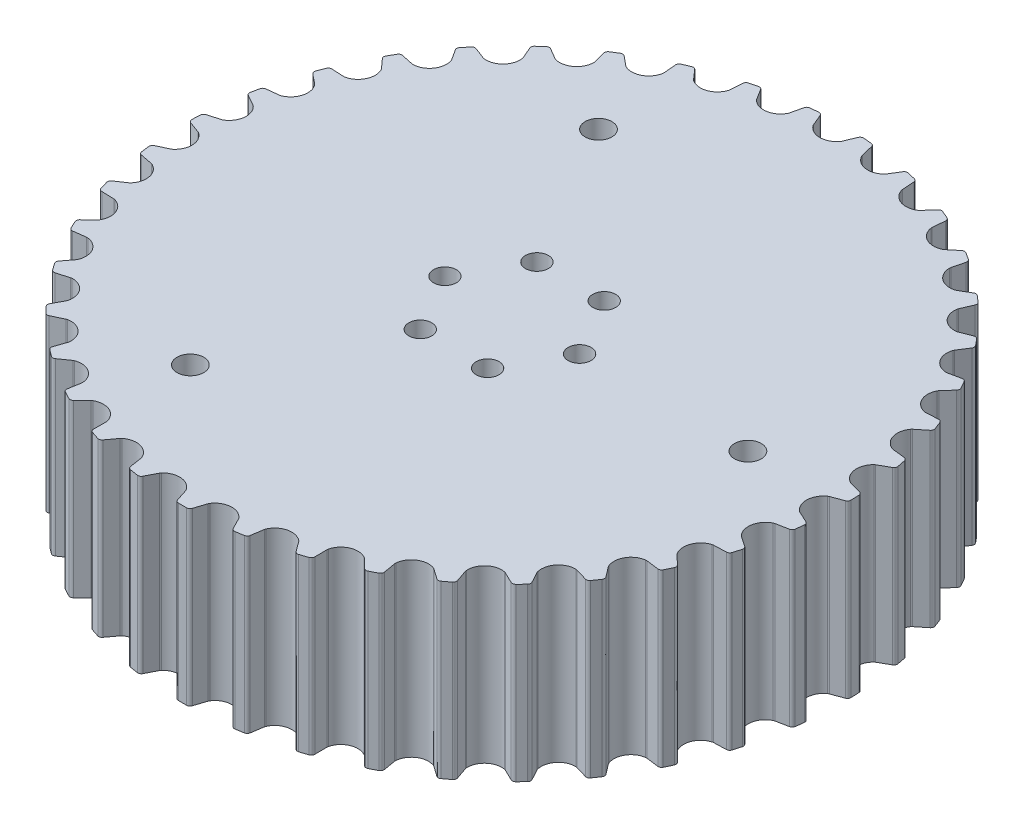
SolidWorks part; units mm, degrees
material "PETG"
ref_plane "Front Plane" through (0, 0, 0) normal (0, 0, 1) x (1, 0, 0)
ref_plane "Top Plane" through (0, 0, 0) normal (0, 1, 0) x (1, 0, 0)
ref_plane "Right Plane" through (0, 0, 0) normal (1, 0, 0) x (0, 0, -1)
sketch "Sketch7" plane through (0, 0, 0) normal (0, 1, 0) x (1, 0, 0)
  line L0 (0, 0) -> (0, 50000) construction
  line L1 (2.1092, 46.8388) -> (2.822, 48.5459)
  line L2 (0, 0) -> (3.9957, 49.4953) construction
  line L3 (0, 0) -> (-3.9957, 49.4953) construction
  line L4 (-2.1092, 46.8388) -> (-2.822, 48.5459)
  line L5 (9.5953, 45.8939) -> (10.5728, 47.4645)
  line L6 (5.4316, 46.5706) -> (5.0018, 48.3699)
  line L7 (16.833, 43.7604) -> (18.0497, 45.1539)
  line L8 (12.8317, 45.0962) -> (12.6961, 46.9412)
  line L9 (23.6346, 40.4935) -> (25.0591, 41.6738)
  line L10 (19.8995, 42.4539) -> (20.0616, 44.2967)
  line L11 (29.8242, 36.1779) -> (31.4196, 37.1143)
  line L12 (26.4519, 38.712) -> (26.9075, 40.5049)
  line L13 (35.2413, 30.9252) -> (36.9663, 31.5937)
  line L14 (32.3192, 33.9675) -> (33.0565, 35.6641)
  line L15 (39.7457, 24.8716) -> (41.5555, 25.2547)
  line L16 (37.3494, 28.3433) -> (38.3494, 29.8997)
  line L17 (43.2207, 18.1739) -> (45.0685, 18.2617)
  line L18 (41.4123, 21.985) -> (42.649, 23.3608)
  line L19 (45.5763, 11.0055) -> (47.4143, 10.7957)
  line L20 (44.4027, 15.0573) -> (45.844, 16.2169)
  line L21 (46.7515, 3.552) -> (48.5321, 3.0501)
  line L22 (46.243, 7.7396) -> (47.8518, 8.653)
  line L23 (46.7159, -3.9935) -> (48.3929, -4.7745)
  line L24 (46.8857, 0.2215) -> (48.6201, 0.865)
  line L25 (45.4703, -11.4355) -> (47.0003, -12.4754)
  line L26 (46.3141, -7.3024) -> (48.1293, -6.9454)
  line L27 (43.0471, -18.5814) -> (44.3905, -19.8532)
  line L28 (44.5429, -14.6371) -> (46.3919, -14.576)
  line L29 (39.509, -25.246) -> (40.6309, -26.7169)
  line L30 (41.6182, -21.5928) -> (43.4529, -21.829)
  line L31 (34.9476, -31.2567) -> (35.8191, -32.8885)
  line L32 (37.6155, -27.9892) -> (39.3886, -28.5167)
  line L33 (29.4811, -36.458) -> (30.0796, -38.2084)
  line L34 (32.6386, -33.6607) -> (34.3042, -34.4658)
  line L35 (23.2511, -40.7149) -> (23.561, -42.5387)
  line L36 (26.8164, -38.4604) -> (28.3312, -39.5222)
  line L37 (16.4188, -43.9174) -> (16.4322, -45.7673)
  line L38 (20.2996, -42.264) -> (21.6245, -43.5551)
  line L39 (9.1614, -45.9825) -> (8.8778, -47.8106)
  line L40 (13.2571, -44.973) -> (14.3578, -46.4599)
  line L41 (1.6666, -46.8566) -> (1.0935, -48.6155)
  line L42 (5.8713, -46.5172) -> (6.7192, -48.1614)
  line L43 (-5.8713, -46.5172) -> (-6.7192, -48.1614)
  line L44 (-1.6666, -46.8566) -> (-1.0935, -48.6155)
  line L45 (-13.2571, -44.973) -> (-14.3578, -46.4599)
  line L46 (-9.1614, -45.9825) -> (-8.8778, -47.8106)
  line L47 (-20.2996, -42.264) -> (-21.6245, -43.5551)
  line L48 (-16.4188, -43.9174) -> (-16.4322, -45.7673)
  line L49 (-26.8164, -38.4604) -> (-28.3312, -39.5222)
  line L50 (-23.2511, -40.7149) -> (-23.561, -42.5387)
  line L51 (-32.6386, -33.6607) -> (-34.3042, -34.4658)
  line L52 (-29.4811, -36.458) -> (-30.0796, -38.2084)
  line L53 (-37.6155, -27.9892) -> (-39.3886, -28.5167)
  line L54 (-34.9476, -31.2567) -> (-35.8191, -32.8885)
  line L55 (-41.6182, -21.5928) -> (-43.4529, -21.829)
  line L56 (-39.509, -25.246) -> (-40.6309, -26.7169)
  line L57 (-44.5429, -14.6371) -> (-46.3919, -14.576)
  line L58 (-43.0471, -18.5814) -> (-44.3905, -19.8532)
  line L59 (-46.3141, -7.3024) -> (-48.1293, -6.9454)
  line L60 (-45.4703, -11.4355) -> (-47.0003, -12.4754)
  line L61 (-46.8857, 0.2215) -> (-48.6201, 0.865)
  line L62 (-46.7159, -3.9935) -> (-48.3929, -4.7745)
  line L63 (0, 0) -> (2.0086, 46.666) construction
  line L64 (-46.243, 7.7396) -> (-47.8518, 8.653)
  line L65 (-46.7515, 3.552) -> (-48.5321, 3.0501)
  line L66 (-44.4027, 15.0573) -> (-45.844, 16.2169)
  line L67 (-45.5763, 11.0055) -> (-47.4143, 10.7957)
  line L68 (-41.4123, 21.985) -> (-42.649, 23.3608)
  line L69 (-43.2207, 18.1739) -> (-45.0685, 18.2617)
  line L70 (-37.3494, 28.3433) -> (-38.3494, 29.8997)
  line L71 (-39.7457, 24.8716) -> (-41.5555, 25.2547)
  line L72 (-32.3192, 33.9675) -> (-33.0565, 35.6641)
  line L73 (-35.2413, 30.9252) -> (-36.9663, 31.5937)
  line L74 (-26.4519, 38.712) -> (-26.9075, 40.5049)
  line L75 (-29.8242, 36.1779) -> (-31.4196, 37.1143)
  line L76 (-19.8995, 42.4539) -> (-20.0616, 44.2967)
  line L77 (-23.6346, 40.4935) -> (-25.0591, 41.6738)
  line L78 (-12.8317, 45.0962) -> (-12.6961, 46.9412)
  line L79 (-16.833, 43.7604) -> (-18.0497, 45.1539)
  line L80 (-5.4316, 46.5706) -> (-5.0018, 48.3699)
  line L81 (-9.5953, 45.8939) -> (-10.5728, 47.4645)
  circle A0 centre (0, 0) radius 49.6563 construction
  circle A1 centre (0, 0) radius 48.97 construction
  arc A2 (2.0086, 46.666) -> (-2.0086, 46.666) centre (0, 48.2207) cw
  arc A3 (2.0086, 46.666) -> (2.1092, 46.8388) centre (1.406, 47.1324) ccw
  arc A4 (2.822, 48.5459) -> (3.3253, 48.857) centre (3.2908, 48.3501) cw
  arc A5 (-2.822, 48.5459) -> (-3.3253, 48.857) centre (-3.2908, 48.3501) ccw
  arc A6 (-2.0086, 46.666) -> (-2.1092, 46.8388) centre (-1.406, 47.1324) cw
  arc A7 (3.3253, 48.857) -> (3.9404, 48.8112) centre (0, 0) cw
  arc A8 (-3.3253, 48.857) -> (-3.9404, 48.8112) centre (0, 0) ccw
  arc A9 (9.4683, 45.7395) -> (5.5032, 46.3839) centre (7.7351, 47.5963) cw
  arc A10 (9.4683, 45.7395) -> (9.5953, 45.8939) centre (8.9484, 46.2965) ccw
  arc A11 (10.5728, 47.4645) -> (11.1195, 47.6909) centre (11.0041, 47.1961) cw
  arc A12 (5.0018, 48.3699) -> (4.555, 48.7577) centre (4.5077, 48.2519) ccw
  arc A13 (5.5032, 46.3839) -> (5.4316, 46.5706) centre (6.1728, 46.7476) cw
  arc A14 (11.1195, 47.6909) -> (11.7193, 47.547) centre (0, 0) cw
  arc A15 (4.555, 48.7577) -> (3.9404, 48.8112) centre (0, 0) ccw
  arc A16 (16.6828, 43.6283) -> (12.8724, 44.9004) centre (15.27, 45.7391) cw
  arc A17 (16.6828, 43.6283) -> (16.833, 43.7604) centre (16.259, 44.2616) ccw
  arc A18 (18.0497, 45.1539) -> (18.6256, 45.2896) centre (18.4324, 44.8197) cw
  arc A19 (12.6961, 46.9412) -> (12.3173, 47.3956) centre (12.1895, 46.9039) ccw
  arc A20 (12.8724, 44.9004) -> (12.8317, 45.0962) centre (13.5917, 45.152) cw
  arc A21 (18.6256, 45.2896) -> (19.1946, 45.0514) centre (0, 0) cw
  arc A22 (12.3173, 47.3956) -> (11.7193, 47.547) centre (0, 0) ccw
  arc A23 (23.4653, 40.3872) -> (19.9082, 42.2541) centre (22.4093, 42.6973) cw
  arc A24 (23.4653, 40.3872) -> (23.6346, 40.4935) centre (23.1485, 41.0803) ccw
  arc A25 (25.0591, 41.6738) -> (25.6494, 41.7153) centre (25.3833, 41.2826) cw
  arc A26 (20.0616, 44.2967) -> (19.7605, 44.806) centre (19.5555, 44.3412) ccw
  arc A27 (19.9082, 42.2541) -> (19.8995, 42.4539) centre (20.6586, 42.3871) cw
  arc A28 (25.6494, 41.7153) -> (26.1728, 41.389) centre (0, 0) cw
  arc A29 (19.7605, 44.806) -> (19.1946, 45.0514) centre (0, 0) ccw
  arc A30 (29.64, 36.1001) -> (26.4285, 38.5134) centre (28.9682, 38.5497) cw
  arc A31 (29.64, 36.1001) -> (29.8242, 36.1779) centre (29.4384, 36.835) ccw
  arc A32 (31.4196, 37.1143) -> (32.0088, 37.0607) centre (31.6768, 36.6762) cw
  arc A33 (26.9075, 40.5049) -> (26.692, 41.056) centre (26.4151, 40.6301) ccw
  arc A34 (26.4285, 38.5134) -> (26.4519, 38.712) centre (27.1904, 38.5243) cw
  arc A35 (32.0088, 37.0607) -> (32.4731, 36.6546) centre (0, 0) cw
  arc A36 (26.692, 41.056) -> (26.1728, 41.389) centre (0, 0) ccw
  arc A37 (35.047, 30.8781) -> (32.2642, 33.7753) centre (34.7769, 33.4037) cw
  arc A38 (35.047, 30.8781) -> (35.2413, 30.9252) centre (34.966, 31.6357) ccw
  arc A39 (36.9663, 31.5937) -> (37.5393, 31.4462) centre (37.1498, 31.1199) cw
  arc A40 (33.0565, 35.6641) -> (32.9322, 36.2426) centre (32.5906, 35.8666) ccw
  arc A41 (32.2642, 33.7753) -> (32.3192, 33.9675) centre (33.018, 33.6638) cw
  arc A42 (37.5393, 31.4462) -> (37.9324, 30.9709) centre (0, 0) cw
  arc A43 (32.9322, 36.2426) -> (32.4731, 36.6546) centre (0, 0) ccw
  arc A44 (39.5464, 24.8563) -> (37.2643, 28.1623) centre (39.6849, 27.3925) cw
  arc A45 (39.5464, 24.8563) -> (39.7457, 24.8716) centre (39.5879, 25.6171) ccw
  arc A46 (41.5555, 25.2547) -> (42.0975, 25.0172) centre (41.6607, 24.7577) cw
  arc A47 (38.3494, 29.8997) -> (38.3195, 30.4906) centre (37.922, 30.1743) ccw
  arc A48 (37.2643, 28.1623) -> (37.3494, 28.3433) centre (37.9905, 27.9314) cw
  arc A49 (42.0975, 25.0172) -> (42.4093, 24.485) centre (0, 0) cw
  arc A50 (38.3195, 30.4906) -> (37.9324, 30.9709) centre (0, 0) ccw
  arc A51 (43.0215, 18.1907) -> (41.2993, 21.82) centre (43.565, 20.6719) cw
  arc A52 (43.0215, 18.1907) -> (43.2207, 18.1739) centre (43.1845, 18.935) ccw
  arc A53 (45.0685, 18.2617) -> (45.5654, 17.9404) centre (45.0927, 17.7542) cw
  arc A54 (42.649, 23.3608) -> (42.7143, 23.9489) centre (42.2712, 23.7004) ccw
  arc A55 (41.2993, 21.82) -> (41.4123, 21.985) centre (41.979, 21.4756) cw
  arc A56 (45.5654, 17.9404) -> (45.7877, 17.365) centre (0, 0) cw
  arc A57 (42.7143, 23.9489) -> (42.4093, 24.485) centre (0, 0) ccw
  arc A58 (45.3823, 11.054) -> (44.2647, 14.9126) centre (46.3169, 13.4158) cw
  arc A59 (45.3823, 11.054) -> (45.5763, 11.0055) centre (45.6627, 11.7626) ccw
  arc A60 (47.4143, 10.7957) -> (47.8532, 10.3988) centre (47.3567, 10.291) cw
  arc A61 (45.844, 16.2169) -> (46.0028, 16.7869) centre (45.5256, 16.6127) ccw
  arc A62 (44.2647, 14.9126) -> (44.4027, 15.0573) centre (44.8803, 14.4636) cw
  arc A63 (47.8532, 10.3988) -> (47.9803, 9.7953) centre (0, 0) cw
  arc A64 (46.0028, 16.7869) -> (45.7877, 17.365) centre (0, 0) ccw
  arc A65 (46.5678, 3.631) -> (46.0836, 7.6189) centre (47.8691, 5.8124) cw
  arc A66 (46.5678, 3.631) -> (46.7515, 3.552) centre (46.9582, 4.2854) ccw
  arc A67 (48.5321, 3.0501) -> (48.9016, 2.588) centre (48.3942, 2.5611) cw
  arc A68 (47.8518, 8.653) -> (48.0999, 9.1901) centre (47.6009, 9.0948) ccw
  arc A69 (46.0836, 7.6189) -> (46.243, 7.7396) centre (46.6193, 7.0769) cw
  arc A70 (48.9016, 2.588) -> (48.9303, 1.9718) centre (0, 0) cw
  arc A71 (48.0999, 9.1901) -> (47.9803, 9.7953) centre (0, 0) ccw
  arc A72 (46.5473, -3.886) -> (46.709, 0.1279) centre (48.1816, -1.9417) cw
  arc A73 (46.5473, -3.886) -> (46.7159, -3.9935) centre (47.0376, -3.3027) ccw
  arc A74 (48.3929, -4.7745) -> (48.6834, -5.2899) centre (48.1784, -5.235) cw
  arc A75 (48.6201, 0.865) -> (48.9512, 1.3553) centre (48.4434, 1.3413) ccw
  arc A76 (46.709, 0.1279) -> (46.8857, 0.2215) centre (47.1508, -0.493) cw
  arc A77 (48.6834, -5.2899) -> (48.613, -5.9027) centre (0, 0) cw
  arc A78 (48.9512, 1.3553) -> (48.9303, 1.9718) centre (0, 0) ccw
  arc A79 (45.3211, -11.3024) -> (46.1247, -7.3664) centre (47.2462, -9.6454) cw
  arc A80 (45.3211, -11.3024) -> (45.4703, -11.4355) centre (45.8986, -10.8053) ccw
  arc A81 (47.0003, -12.4754) -> (47.2045, -13.0308) centre (46.7147, -12.8956) cw
  arc A82 (48.1293, -6.9454) -> (48.5347, -6.5145) centre (48.0312, -6.447) ccw
  arc A83 (46.1247, -7.3664) -> (46.3141, -7.3024) centre (46.4611, -8.0501) cw
  arc A84 (47.2045, -13.0308) -> (47.0366, -13.6243) centre (0, 0) cw
  arc A85 (48.5347, -6.5145) -> (48.613, -5.9027) centre (0, 0) ccw
  arc A86 (42.9212, -18.426) -> (44.3457, -14.6699) centre (45.0871, -17.0993) cw
  arc A87 (42.9212, -18.426) -> (43.0471, -18.5814) centre (43.571, -18.028) ccw
  arc A88 (44.3905, -19.8532) -> (44.5029, -20.4341) centre (44.0412, -20.2221) cw
  arc A89 (46.3919, -14.576) -> (46.8612, -14.2157) centre (46.3751, -14.0682) ccw
  arc A90 (44.3457, -14.6699) -> (44.5429, -14.6371) centre (44.5681, -15.3987) cw
  arc A91 (44.5029, -20.4341) -> (44.242, -20.9931) centre (0, 0) cw
  arc A92 (46.8612, -14.2157) -> (47.0366, -13.6243) centre (0, 0) ccw
  arc A93 (39.4096, -25.0725) -> (41.4182, -21.5935) centre (41.7604, -24.1103) cw
  arc A94 (39.4096, -25.0725) -> (39.509, -25.246) centre (40.1148, -24.7838) ccw
  arc A95 (40.6309, -26.7169) -> (40.6487, -27.3083) centre (40.227, -27.025) cw
  arc A96 (43.4529, -21.829) -> (43.974, -21.5487) centre (43.5178, -21.3251) ccw
  arc A97 (41.4182, -21.5935) -> (41.6182, -21.5928) centre (41.5209, -22.3486) cw
  arc A98 (40.6487, -27.3083) -> (40.3015, -27.8181) centre (0, 0) cw
  arc A99 (43.974, -21.5487) -> (44.242, -20.9931) centre (0, 0) ccw
  arc A100 (34.8774, -31.0695) -> (37.418, -27.9578) centre (37.352, -30.497) cw
  arc A101 (34.8774, -31.0695) -> (34.9476, -31.2567) centre (35.6198, -30.8978) ccw
  arc A102 (35.8191, -32.8885) -> (35.7418, -33.4752) centre (35.371, -33.1279) cw
  arc A103 (39.3886, -28.5167) -> (39.9479, -28.3236) centre (39.5335, -28.0297) ccw
  arc A104 (37.418, -27.9578) -> (37.6155, -27.9892) centre (37.3982, -28.7196) cw
  arc A105 (35.7418, -33.4752) -> (35.3173, -33.9227) centre (0, 0) cw
  arc A106 (39.9479, -28.3236) -> (40.3015, -27.8181) centre (0, 0) ccw
  arc A107 (29.4418, -36.2619) -> (32.4487, -33.598) centre (31.9762, -36.0937) cw
  arc A108 (29.4418, -36.2619) -> (29.4811, -36.458) centre (30.2021, -36.2115) ccw
  arc A109 (30.0796, -38.2084) -> (29.9091, -38.7751) centre (29.5988, -38.3728) cw
  arc A110 (34.3042, -34.4658) -> (34.8872, -34.3649) centre (34.5253, -34.0084) ccw
  arc A111 (32.4487, -33.598) -> (32.6386, -33.6607) centre (32.307, -34.3467) cw
  arc A112 (29.9091, -38.7751) -> (29.4183, -39.1487) centre (0, 0) cw
  arc A113 (34.8872, -34.3649) -> (35.3173, -33.9227) centre (0, 0) ccw
  arc A114 (23.2437, -40.5151) -> (26.639, -38.3681) centre (25.7723, -40.7557) cw
  arc A115 (23.2437, -40.5151) -> (23.2511, -40.7149) centre (24.0023, -40.5873) ccw
  arc A116 (23.561, -42.5387) -> (23.3019, -43.0707) centre (23.0601, -42.6238) cw
  arc A117 (28.3312, -39.5222) -> (28.9229, -39.5162) centre (28.6228, -39.1062) ccw
  arc A118 (26.639, -38.3681) -> (26.8164, -38.4604) centre (26.379, -39.0844) cw
  arc A119 (23.3019, -43.0707) -> (22.7575, -43.3608) centre (0, 0) cw
  arc A120 (28.9229, -39.5162) -> (29.4183, -39.1487) centre (0, 0) ccw
  arc A121 (16.4436, -43.719) -> (20.1394, -42.1444) centre (18.9009, -44.3621) cw
  arc A122 (16.4436, -43.719) -> (16.4188, -43.9174) centre (17.1808, -43.9119) ccw
  arc A123 (16.4322, -45.7673) -> (16.0911, -46.2508) centre (15.9241, -45.771) cw
  arc A124 (21.6245, -43.5551) -> (22.2095, -43.644) centre (21.9791, -43.1912) ccw
  arc A125 (20.1394, -42.1444) -> (20.2996, -42.264) centre (19.7678, -42.8097) cw
  arc A126 (16.0911, -46.2508) -> (15.5072, -46.4498) centre (0, 0) cw
  arc A127 (22.2095, -43.644) -> (22.7575, -43.3608) centre (0, 0) ccw
  arc A128 (9.2177, -45.7906) -> (13.1181, -44.8293) centre (11.54, -46.8195) cw
  arc A129 (9.2177, -45.7906) -> (9.1614, -45.9825) centre (9.9144, -46.0993) ccw
  arc A130 (8.8778, -47.8106) -> (8.4636, -48.2331) centre (8.3757, -47.7327) cw
  arc A131 (14.3578, -46.4599) -> (14.9209, -46.6415) centre (14.7661, -46.1576) ccw
  arc A132 (13.1181, -44.8293) -> (13.2571, -44.973) centre (12.6447, -45.4263) cw
  arc A133 (8.4636, -48.2331) -> (7.8553, -48.3359) centre (0, 0) cw
  arc A134 (14.9209, -46.6415) -> (15.5072, -46.4498) centre (0, 0) ccw
  arc A135 (1.753, -46.6763) -> (5.7571, -46.353) centre (3.8802, -48.0643) cw
  arc A136 (1.753, -46.6763) -> (1.6666, -46.8566) centre (2.3911, -47.0927) ccw
  arc A137 (1.0935, -48.6155) -> (0.6168, -48.9661) centre (0.6104, -48.4581) cw
  arc A138 (6.7192, -48.1614) -> (7.2459, -48.431) centre (7.1707, -47.9285) ccw
  arc A139 (5.7571, -46.353) -> (5.8713, -46.5172) centre (5.194, -46.8664) cw
  arc A140 (0.6168, -48.9661) -> (0, -48.97) centre (0, 0) cw
  arc A141 (7.2459, -48.431) -> (7.8553, -48.3359) centre (0, 0) ccw
  arc A142 (-5.7571, -46.353) -> (-1.753, -46.6763) centre (-3.8802, -48.0643) cw
  arc A143 (-5.7571, -46.353) -> (-5.8713, -46.5172) centre (-5.194, -46.8664) ccw
  arc A144 (-6.7192, -48.1614) -> (-7.2459, -48.431) centre (-7.1707, -47.9285) cw
  arc A145 (-1.0935, -48.6155) -> (-0.6168, -48.9661) centre (-0.6104, -48.4581) ccw
  arc A146 (-1.753, -46.6763) -> (-1.6666, -46.8566) centre (-2.3911, -47.0927) cw
  arc A147 (-7.2459, -48.431) -> (-7.8553, -48.3359) centre (0, 0) cw
  arc A148 (-0.6168, -48.9661) -> (0, -48.97) centre (0, 0) ccw
  arc A149 (-13.1181, -44.8293) -> (-9.2177, -45.7906) centre (-11.54, -46.8195) cw
  arc A150 (-13.1181, -44.8293) -> (-13.2571, -44.973) centre (-12.6447, -45.4263) ccw
  arc A151 (-14.3578, -46.4599) -> (-14.9209, -46.6415) centre (-14.7661, -46.1576) cw
  arc A152 (-8.8778, -47.8106) -> (-8.4636, -48.2331) centre (-8.3757, -47.7327) ccw
  arc A153 (-9.2177, -45.7906) -> (-9.1614, -45.9825) centre (-9.9144, -46.0993) cw
  arc A154 (-14.9209, -46.6415) -> (-15.5072, -46.4498) centre (0, 0) cw
  arc A155 (-8.4636, -48.2331) -> (-7.8553, -48.3359) centre (0, 0) ccw
  arc A156 (-20.1394, -42.1444) -> (-16.4436, -43.719) centre (-18.9009, -44.3621) cw
  arc A157 (-20.1394, -42.1444) -> (-20.2996, -42.264) centre (-19.7678, -42.8097) ccw
  arc A158 (-21.6245, -43.5551) -> (-22.2095, -43.644) centre (-21.9791, -43.1912) cw
  arc A159 (-16.4322, -45.7673) -> (-16.0911, -46.2508) centre (-15.9241, -45.771) ccw
  arc A160 (-16.4436, -43.719) -> (-16.4188, -43.9174) centre (-17.1808, -43.9119) cw
  arc A161 (-22.2095, -43.644) -> (-22.7575, -43.3608) centre (0, 0) cw
  arc A162 (-16.0911, -46.2508) -> (-15.5072, -46.4498) centre (0, 0) ccw
  arc A163 (-26.639, -38.3681) -> (-23.2437, -40.5151) centre (-25.7723, -40.7557) cw
  arc A164 (-26.639, -38.3681) -> (-26.8164, -38.4604) centre (-26.379, -39.0844) ccw
  arc A165 (-28.3312, -39.5222) -> (-28.9229, -39.5162) centre (-28.6228, -39.1062) cw
  arc A166 (-23.561, -42.5387) -> (-23.3019, -43.0707) centre (-23.0601, -42.6238) ccw
  arc A167 (-23.2437, -40.5151) -> (-23.2511, -40.7149) centre (-24.0023, -40.5873) cw
  arc A168 (-28.9229, -39.5162) -> (-29.4183, -39.1487) centre (0, 0) cw
  arc A169 (-23.3019, -43.0707) -> (-22.7575, -43.3608) centre (0, 0) ccw
  arc A170 (-32.4487, -33.598) -> (-29.4418, -36.2619) centre (-31.9762, -36.0937) cw
  arc A171 (-32.4487, -33.598) -> (-32.6386, -33.6607) centre (-32.307, -34.3467) ccw
  arc A172 (-34.3042, -34.4658) -> (-34.8872, -34.3649) centre (-34.5253, -34.0084) cw
  arc A173 (-30.0796, -38.2084) -> (-29.9091, -38.7751) centre (-29.5988, -38.3728) ccw
  arc A174 (-29.4418, -36.2619) -> (-29.4811, -36.458) centre (-30.2021, -36.2115) cw
  arc A175 (-34.8872, -34.3649) -> (-35.3173, -33.9227) centre (0, 0) cw
  arc A176 (-29.9091, -38.7751) -> (-29.4183, -39.1487) centre (0, 0) ccw
  arc A177 (-37.418, -27.9578) -> (-34.8774, -31.0695) centre (-37.352, -30.497) cw
  arc A178 (-37.418, -27.9578) -> (-37.6155, -27.9892) centre (-37.3982, -28.7196) ccw
  arc A179 (-39.3886, -28.5167) -> (-39.9479, -28.3236) centre (-39.5335, -28.0297) cw
  arc A180 (-35.8191, -32.8885) -> (-35.7418, -33.4752) centre (-35.371, -33.1279) ccw
  arc A181 (-34.8774, -31.0695) -> (-34.9476, -31.2567) centre (-35.6198, -30.8978) cw
  arc A182 (-39.9479, -28.3236) -> (-40.3015, -27.8181) centre (0, 0) cw
  arc A183 (-35.7418, -33.4752) -> (-35.3173, -33.9227) centre (0, 0) ccw
  arc A184 (-41.4182, -21.5935) -> (-39.4096, -25.0725) centre (-41.7604, -24.1104) cw
  arc A185 (-41.4182, -21.5935) -> (-41.6182, -21.5928) centre (-41.5209, -22.3486) ccw
  arc A186 (-43.4529, -21.829) -> (-43.974, -21.5487) centre (-43.5178, -21.3251) cw
  arc A187 (-40.6309, -26.7169) -> (-40.6487, -27.3083) centre (-40.227, -27.025) ccw
  arc A188 (-39.4096, -25.0725) -> (-39.509, -25.246) centre (-40.1148, -24.7838) cw
  arc A189 (-43.974, -21.5487) -> (-44.242, -20.9931) centre (0, 0) cw
  arc A190 (-40.6487, -27.3083) -> (-40.3015, -27.8181) centre (0, 0) ccw
  arc A191 (-44.3457, -14.6699) -> (-42.9212, -18.426) centre (-45.0871, -17.0993) cw
  arc A192 (-44.3457, -14.6699) -> (-44.5429, -14.6371) centre (-44.5681, -15.3987) ccw
  arc A193 (-46.3919, -14.576) -> (-46.8612, -14.2157) centre (-46.3751, -14.0682) cw
  arc A194 (-44.3905, -19.8532) -> (-44.5029, -20.4341) centre (-44.0412, -20.2221) ccw
  arc A195 (-42.9212, -18.426) -> (-43.0471, -18.5814) centre (-43.571, -18.028) cw
  arc A196 (-46.8612, -14.2157) -> (-47.0366, -13.6243) centre (0, 0) cw
  arc A197 (-44.5029, -20.4341) -> (-44.242, -20.9931) centre (0, 0) ccw
  arc A198 (-46.1247, -7.3664) -> (-45.3211, -11.3024) centre (-47.2462, -9.6454) cw
  arc A199 (-46.1247, -7.3664) -> (-46.3141, -7.3024) centre (-46.4611, -8.0501) ccw
  arc A200 (-48.1293, -6.9454) -> (-48.5347, -6.5145) centre (-48.0312, -6.447) cw
  arc A201 (-47.0003, -12.4754) -> (-47.2045, -13.0308) centre (-46.7147, -12.8956) ccw
  arc A202 (-45.3211, -11.3024) -> (-45.4703, -11.4355) centre (-45.8986, -10.8053) cw
  arc A203 (-48.5347, -6.5145) -> (-48.613, -5.9027) centre (0, 0) cw
  arc A204 (-47.2045, -13.0308) -> (-47.0366, -13.6243) centre (0, 0) ccw
  arc A205 (-46.709, 0.1279) -> (-46.5473, -3.886) centre (-48.1816, -1.9417) cw
  arc A206 (-46.709, 0.1279) -> (-46.8857, 0.2215) centre (-47.1508, -0.493) ccw
  arc A207 (-48.6201, 0.865) -> (-48.9512, 1.3553) centre (-48.4434, 1.3413) cw
  arc A208 (-48.3929, -4.7745) -> (-48.6834, -5.2899) centre (-48.1784, -5.235) ccw
  arc A209 (-46.5473, -3.886) -> (-46.7159, -3.9935) centre (-47.0376, -3.3027) cw
  arc A210 (-48.9512, 1.3553) -> (-48.9303, 1.9718) centre (0, 0) cw
  arc A211 (-48.6834, -5.2899) -> (-48.613, -5.9027) centre (0, 0) ccw
  arc A212 (-46.0836, 7.6189) -> (-46.5678, 3.631) centre (-47.8691, 5.8124) cw
  arc A213 (-46.0836, 7.6189) -> (-46.243, 7.7396) centre (-46.6193, 7.0769) ccw
  arc A214 (-47.8518, 8.653) -> (-48.0999, 9.1901) centre (-47.6009, 9.0948) cw
  arc A215 (-48.5321, 3.0501) -> (-48.9016, 2.588) centre (-48.3942, 2.5611) ccw
  arc A216 (-46.5678, 3.631) -> (-46.7515, 3.552) centre (-46.9582, 4.2854) cw
  arc A217 (-48.0999, 9.1901) -> (-47.9803, 9.7953) centre (0, 0) cw
  arc A218 (-48.9016, 2.588) -> (-48.9303, 1.9718) centre (0, 0) ccw
  arc A219 (-44.2647, 14.9126) -> (-45.3823, 11.054) centre (-46.3169, 13.4158) cw
  arc A220 (-44.2647, 14.9126) -> (-44.4027, 15.0573) centre (-44.8803, 14.4636) ccw
  arc A221 (-45.844, 16.2169) -> (-46.0028, 16.7869) centre (-45.5256, 16.6127) cw
  arc A222 (-47.4143, 10.7957) -> (-47.8532, 10.3988) centre (-47.3567, 10.291) ccw
  arc A223 (-45.3823, 11.054) -> (-45.5763, 11.0055) centre (-45.6627, 11.7626) cw
  arc A224 (-46.0028, 16.7869) -> (-45.7877, 17.365) centre (0, 0) cw
  arc A225 (-47.8532, 10.3988) -> (-47.9803, 9.7953) centre (0, 0) ccw
  arc A226 (-41.2993, 21.82) -> (-43.0215, 18.1907) centre (-43.565, 20.6719) cw
  arc A227 (-41.2993, 21.82) -> (-41.4123, 21.985) centre (-41.979, 21.4756) ccw
  arc A228 (-42.649, 23.3608) -> (-42.7143, 23.9489) centre (-42.2712, 23.7004) cw
  arc A229 (-45.0685, 18.2617) -> (-45.5654, 17.9404) centre (-45.0927, 17.7542) ccw
  arc A230 (-43.0215, 18.1907) -> (-43.2207, 18.1739) centre (-43.1845, 18.935) cw
  arc A231 (-42.7143, 23.9489) -> (-42.4093, 24.485) centre (0, 0) cw
  arc A232 (-45.5654, 17.9404) -> (-45.7877, 17.365) centre (0, 0) ccw
  arc A233 (-37.2643, 28.1623) -> (-39.5464, 24.8563) centre (-39.6849, 27.3925) cw
  arc A234 (-37.2643, 28.1623) -> (-37.3494, 28.3433) centre (-37.9905, 27.9314) ccw
  arc A235 (-38.3494, 29.8997) -> (-38.3195, 30.4906) centre (-37.922, 30.1743) cw
  arc A236 (-41.5555, 25.2547) -> (-42.0975, 25.0172) centre (-41.6607, 24.7577) ccw
  arc A237 (-39.5464, 24.8563) -> (-39.7457, 24.8716) centre (-39.5879, 25.6171) cw
  arc A238 (-38.3195, 30.4906) -> (-37.9324, 30.9709) centre (0, 0) cw
  arc A239 (-42.0975, 25.0172) -> (-42.4093, 24.485) centre (0, 0) ccw
  arc A240 (-32.2642, 33.7753) -> (-35.047, 30.8781) centre (-34.7769, 33.4037) cw
  arc A241 (-32.2642, 33.7753) -> (-32.3192, 33.9675) centre (-33.018, 33.6638) ccw
  arc A242 (-33.0565, 35.6641) -> (-32.9322, 36.2426) centre (-32.5906, 35.8666) cw
  arc A243 (-36.9663, 31.5937) -> (-37.5393, 31.4462) centre (-37.1498, 31.1199) ccw
  arc A244 (-35.047, 30.8781) -> (-35.2413, 30.9252) centre (-34.966, 31.6357) cw
  arc A245 (-32.9322, 36.2426) -> (-32.4731, 36.6546) centre (0, 0) cw
  arc A246 (-37.5393, 31.4462) -> (-37.9324, 30.9709) centre (0, 0) ccw
  arc A247 (-26.4285, 38.5134) -> (-29.64, 36.1001) centre (-28.9682, 38.5497) cw
  arc A248 (-26.4285, 38.5134) -> (-26.4519, 38.712) centre (-27.1904, 38.5243) ccw
  arc A249 (-26.9075, 40.5049) -> (-26.692, 41.056) centre (-26.4151, 40.6301) cw
  arc A250 (-31.4196, 37.1143) -> (-32.0088, 37.0607) centre (-31.6768, 36.6762) ccw
  arc A251 (-29.64, 36.1001) -> (-29.8242, 36.1779) centre (-29.4384, 36.835) cw
  arc A252 (-26.692, 41.056) -> (-26.1728, 41.389) centre (0, 0) cw
  arc A253 (-32.0088, 37.0607) -> (-32.4731, 36.6546) centre (0, 0) ccw
  arc A254 (-19.9082, 42.2541) -> (-23.4653, 40.3872) centre (-22.4093, 42.6973) cw
  arc A255 (-19.9082, 42.2541) -> (-19.8995, 42.4539) centre (-20.6586, 42.3871) ccw
  arc A256 (-20.0616, 44.2967) -> (-19.7605, 44.806) centre (-19.5555, 44.3412) cw
  arc A257 (-25.0591, 41.6738) -> (-25.6494, 41.7153) centre (-25.3833, 41.2826) ccw
  arc A258 (-23.4653, 40.3872) -> (-23.6346, 40.4935) centre (-23.1485, 41.0803) cw
  arc A259 (-19.7605, 44.806) -> (-19.1946, 45.0514) centre (0, 0) cw
  arc A260 (-25.6494, 41.7153) -> (-26.1728, 41.389) centre (0, 0) ccw
  arc A261 (-12.8724, 44.9004) -> (-16.6828, 43.6283) centre (-15.27, 45.7391) cw
  arc A262 (-12.8724, 44.9004) -> (-12.8317, 45.0962) centre (-13.5917, 45.152) ccw
  arc A263 (-12.6961, 46.9412) -> (-12.3173, 47.3956) centre (-12.1895, 46.9039) cw
  arc A264 (-18.0497, 45.1539) -> (-18.6256, 45.2896) centre (-18.4324, 44.8197) ccw
  arc A265 (-16.6828, 43.6283) -> (-16.833, 43.7604) centre (-16.259, 44.2616) cw
  arc A266 (-12.3173, 47.3956) -> (-11.7193, 47.547) centre (0, 0) cw
  arc A267 (-18.6256, 45.2896) -> (-19.1946, 45.0514) centre (0, 0) ccw
  arc A268 (-5.5032, 46.3839) -> (-9.4683, 45.7395) centre (-7.7351, 47.5963) cw
  arc A269 (-5.5032, 46.3839) -> (-5.4316, 46.5706) centre (-6.1728, 46.7476) ccw
  arc A270 (-5.0018, 48.3699) -> (-4.555, 48.7577) centre (-4.5077, 48.2519) cw
  arc A271 (-10.5728, 47.4645) -> (-11.1195, 47.6909) centre (-11.0041, 47.1961) ccw
  arc A272 (-9.4683, 45.7395) -> (-9.5953, 45.8939) centre (-8.9484, 46.2965) cw
  arc A273 (-4.555, 48.7577) -> (-3.9404, 48.8112) centre (0, 0) cw
  arc A274 (-11.1195, 47.6909) -> (-11.7193, 47.547) centre (0, 0) ccw
  point P14 (0, 48.97)
  dimension "D1" = 99.3127
  dimension "D2" = 97.94
  dimension "D3" = 2.54
  dimension "D5" = 0.762
  dimension "D6" = 0.508
  dimension "D4" = 22.664
  dimension "D7" = 0.7493
  dimension "D9" = 4.0172
  dimension "D8" = 8
  dimension "D10" = 39
extrude "Boss-Extrude5" add sketch "Sketch7" along normal mid plane 25.4 contours A271 A274 A266 A263 L78 A262 A261 A265 L79 A264 A267 A259 A256 L76 A255 A254 A258 L77 A257 A260 A252 A249 L74 A248 A247 A251 L75 A250 A253 A245 A242 L72 A241 A240 A244 L73 A243 A246 A238 A235 L70 A234 A233 A237 L71 A236 A239 A231 A228 L68 A227 region at (0, 0, 0)
sketch "Sketch2" plane through (0, 12.7, 0) normal (0, 1, 0) x (1, 0, 0)
  circle A0 centre (0, 0) radius 54.6563
  dimension "D1" = 109.3127
extrude "Boss-Extrude2" [suppressed] add sketch "Sketch2" along normal blind 1
sketch "Sketch3" plane through (0, -12.7, 0) normal (0, 1, 0) x (1, 0, 0)
  line L0 (0, 0) -> (10, 0) construction
  circle A0 centre (10, 0) radius 1.7
  circle A1 centre (5, -8.6603) radius 1.7
  circle A2 centre (-5, -8.6603) radius 1.7
  circle A3 centre (-10, 0) radius 1.7
  circle A4 centre (-5, 8.6603) radius 1.7
  circle A5 centre (5, 8.6603) radius 1.7
  dimension "D1" = 10
  dimension "D2" = 3.4
  dimension "D3" = 6
extrude "Cut-Extrude1" cut sketch "Sketch3" along normal through all
sketch "Sketch4" plane through (0, -12.7, 0) normal (0, 1, 0) x (1, 0, 0)
  line L0 (0, 0) -> (5, -8.6603) construction
  circle A0 centre (5, -8.6603) radius 3
  circle A1 centre (-5, -8.6603) radius 3
  circle A2 centre (-10, 0) radius 3
  circle A3 centre (-5, 8.6603) radius 3
  circle A4 centre (5, 8.6603) radius 3
  circle A5 centre (10, 0) radius 3
  dimension "D1" = 6
  dimension "D2" = 6
extrude "Cut-Extrude2" [suppressed] cut sketch "Sketch4" along normal offset from surface (13 mm away) 10 up to face at (10, -12.7, 1.7)
sketch "Sketch6" plane through (0, -12.7, 0) normal (0, -1, 0) x (1, 0, 0)
  line L0 (0, 0) -> (35, 0) construction
  circle A0 centre (35, 0) radius 1.985
  circle A1 centre (-17.5, -30.3109) radius 1.985
  circle A2 centre (-17.5, 30.3109) radius 1.985
  dimension "D2" = 3.97
  dimension "D1" = 35
extrude "Cut-Extrude3" cut sketch "Sketch6" against normal through all
equation "\"pitch\"= 8mm"
equation "\"n\"= 39"
equation "\"pitch_dia\"= \"pitch\" * \"n\" / PI"
equation "\"outside_dia\"= 97.94'From manual. For 39 teeth"
equation "\"belt_width\"= 22mm"
equation "\"D1@Sketch2\"=\"pitch_dia\"+10.00mm"
equation "\"tol_dia_id_intfc\" = 0.0200mm ' For hole diameters - Interference fit"
equation "\"tol_dia_id_slip\"  = 0.0300mm ' For hole diameters - Slip fit"
equation "\"tol_dia_id_clear\" = 0.0500mm ' For hole diameters - Clearance fit"
equation "\"tol_dia_od_intfc\" = 0.0200mm ' For shaft diameters - Interference fit"
equation "\"tol_dia_od_slip\"  = 0.0300mm ' For shaft diameters - Slip fit"
equation "\"tol_dia_od_clear\" = 0.0500mm ' For shaft diameters - Clearance fit"
equation "\"tol_general_intfc\"= 0.0030mm ' For general parts (Horiz) - Interference fit"
equation "\"tol_general_slip\" = 0.0050mm ' For general parts (Horiz) - Slip fit"
equation "\"tol_general_clear\"= 0.0100mm ' For general parts (Horiz) - Clearance fit"
equation "\"tol_layer_intfc\"  = 0.0030mm ' For all parts (Vert) - Interference fit"
equation "\"tol_layer_slip\"   = 0.0050mm ' For all parts (Vert) - Slip fit"
equation "\"tol_layer_clear\"  = 0.0100mm ' For all parts (Vert) - Clearance fit"
equation "\"tol_corner_rad\"   = 0.100mm ' For corners that fit into other parts"
equation "\"D2@Sketch6\"=3.95+\"tol_dia_id_intfc\""
equation "\"D1@Sketch7\"=\"pitch_dia\""
equation "\"D2@Sketch7\"=\"outside_dia\""
equation "\"D8@Sketch7\"=\"pitch\""
equation "\"D10@Sketch7\"=\"n\""
equation "\"D1@Boss-Extrude5\"= \"belt_width\""
